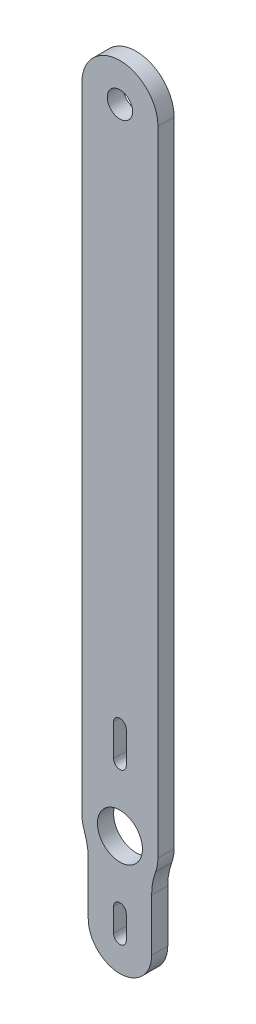
SolidWorks part; units mm, degrees
ref_plane "Front Plane" through (0, 0, 0) normal (0, 0, 1) x (1, 0, 0)
ref_plane "Top Plane" through (0, 0, 0) normal (0, 1, 0) x (1, 0, 0)
ref_plane "Right Plane" through (0, 0, 0) normal (1, 0, 0) x (0, 0, -1)
sketch "Model" plane through (0, 0, 0) normal (0, 0, 1) x (1, 0, 0)
  line L0 (-1, 18.4215) -> (-1, -3.4062) construction
  line L1 (1, 18.4215) -> (1, 5.9161) construction
  line L2 (-6, 0) -> (-6, 100)
  line L3 (6, 0) -> (6, 100)
  line L7 (-7.5978, 10.1) -> (4.5933, 10.1) construction
  line L8 (-1.9126, -10.1) -> (1, -10.1) construction
  line L9 (-3.5953, 15.1) -> (3.0222, 15.1) construction
  line L10 (-2.3019, -13.8) -> (3.0222, -13.8) construction
  line L13 (-1, -10.1) -> (-1, -13.8)
  line L14 (1, -10.1) -> (1, -13.8)
  line L15 (-1, 15.1) -> (-1, 10.1)
  line L16 (1, 15.1) -> (1, 10.1)
  line L17 (1, 3.4062) -> (1, -5.9161) construction
  line L18 (1, -10.1) -> (1, -18.7667) construction
  line L19 (-1, -5.9161) -> (-1, -18.7667) construction
  line L20 (-5, -5.5678) -> (-5, -13.8)
  line L21 (5, -5.5678) -> (5, -13.8)
  circle A0 centre (0, 0) radius 3.55
  arc A1 (-6, 0) -> (-5.625, -2.0879) centre (0, 0) ccw
  arc A2 (1, 15.1) -> (-1, 15.1) centre (0, 15.1) ccw
  arc A3 (-1, 10.1) -> (1, 10.1) centre (0, 10.1) ccw
  arc A4 (1, -10.1) -> (-1, -10.1) centre (0, -10.1) ccw
  arc A5 (-1, -13.8) -> (1, -13.8) centre (0, -13.8) ccw
  arc A6 (6, 100) -> (-6, 100) centre (0, 100) ccw
  circle A7 centre (0, 100) radius 2
  arc A8 (-5, -13.8) -> (5, -13.8) centre (0, -13.8) ccw
  arc A9 (5.625, -2.0879) -> (6, 0) centre (0, 0) ccw
  arc A11 (5.625, -2.0879) -> (5, -5.5678) centre (15, -5.5678) ccw
  arc A12 (-5.625, -2.0879) -> (-5, -5.5678) centre (-15, -5.5678) cw
  point P44 (5, -3.3166)
  point P47 (-5, -3.3166)
  dimension "D1" = 7.1
  dimension "D2" = 12
  dimension "D5" = 4
  dimension "D6" = 100
  dimension "D3" = 1
  dimension "D4" = 1
  dimension "D9" = 10.1
  dimension "D10" = 10.1
  dimension "D11" = 3.7
  dimension "D12" = 5
extrude "Boss-Extrude1" add sketch "Model" along normal blind 2.55
